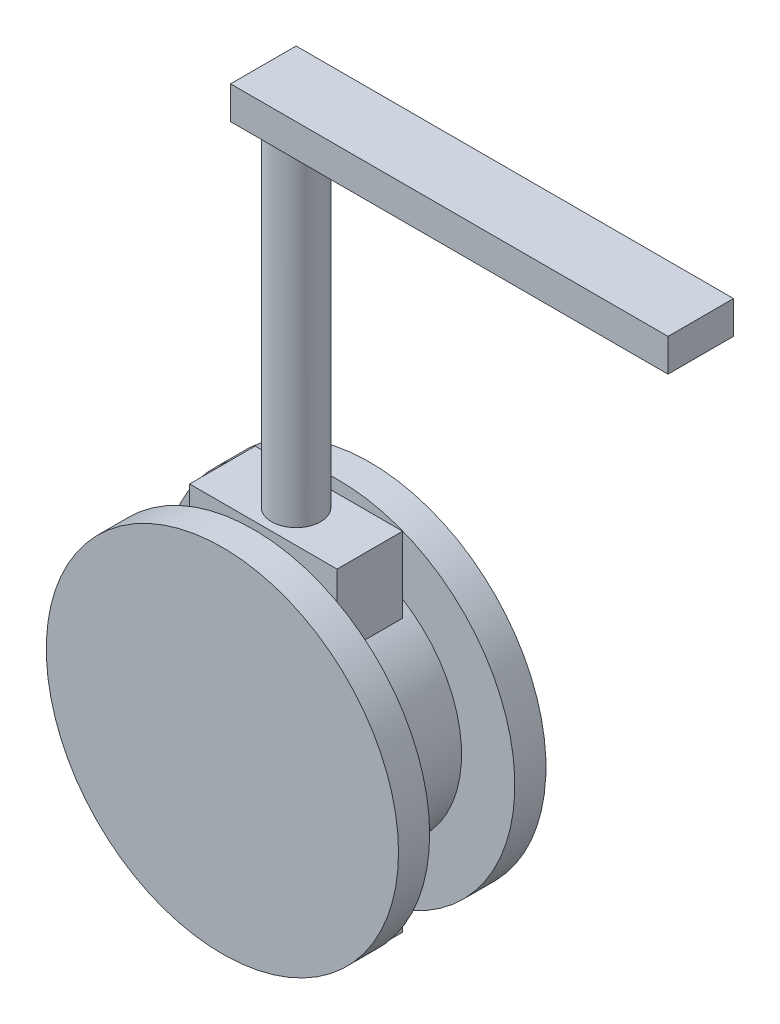
SolidWorks part; units mm, degrees
ref_plane "Плоскость1" through (0, 0, 0) normal (0, 0, 1) x (1, 0, 0)
ref_plane "Плоскость2" through (0, 0, 0) normal (0, 1, 0) x (1, 0, 0)
ref_plane "Плоскость3" through (0, 0, 0) normal (1, 0, 0) x (0, 0, -1)
sketch "Эскиз1" plane through (0, 0, 0) normal (0, 0, 1) x (1, 0, 0)
  circle A0 centre (0, 0) radius 75
  dimension "D1" = 150
extrude "ОснованиеЗатвора" add sketch "Эскиз1" along normal mid plane 52
sketch "Эскиз2" plane through (0, 0, 0) normal (0, 1, 0) x (1, 0, 0)
  circle A0 centre (0, 0) radius 15
  dimension "D1" = 30
extrude "Шток" add sketch "Эскиз2" along normal blind 330
sketch "Эскиз3" plane through (0, 330, 0) normal (0, 1, 0) x (-1, 0, 0)
  line L1 (-247, -20) -> (20, -20)
  line L2 (-247, -20) -> (-247, 20)
  line L3 (-247, 20) -> (20, 20)
  line L4 (20, -20) -> (20, 20)
  dimension "D1" = 40
  dimension "D2" = 20
  dimension "D3" = 20
  dimension "D4" = 267
extrude "Рукоятка" add sketch "Эскиз3" against normal blind 20
sketch "Эскиз4" plane through (0, 0, 0) normal (0, 1, 0) x (1, 0, 0)
  line L1 (-45, 20) -> (45, 20)
  line L2 (-45, 20) -> (-45, -20)
  line L3 (-45, -20) -> (45, -20)
  line L4 (45, 20) -> (45, -20)
  dimension "D1" = 90
  dimension "D2" = 40
  dimension "D3" = 45
  dimension "D4" = 20
extrude "КреплениеЗатвора" add sketch "Эскиз4" along normal mid plane 212
sketch "Эскиз5" plane through (0, 0, 26) normal (0, 0, 1) x (1, 0, 0)
  circle A0 centre (0, 0) radius 107.5
  dimension "D1" = 215
extrude "Фланец1" add sketch "Эскиз5" along normal blind 19
sketch "Эскиз6" plane through (0, 0, -26) normal (0, 0, -1) x (-1, 0, 0)
  circle A0 centre (0, 0) radius 107.5
  dimension "D1" = 215
extrude "Фланец2" add sketch "Эскиз6" along normal blind 19
ref_axis "Ось1" through (0, 0, 56.4951) along (0, 0, -1)
